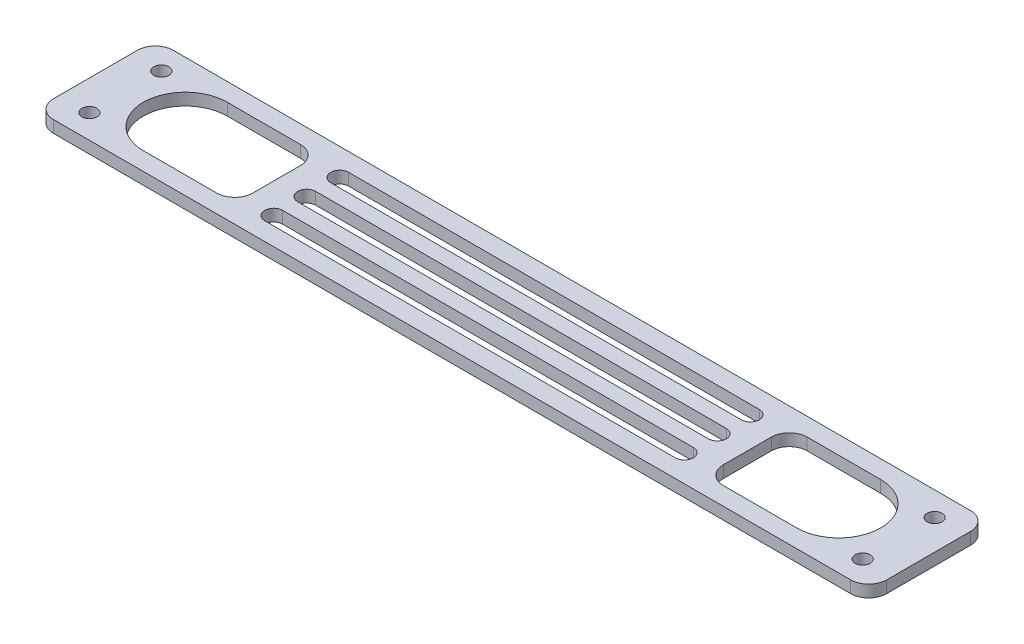
SolidWorks part; units mm, degrees
material "Thornel Mat VMA"
ref_plane "前视基准面" through (0, 0, 0) normal (0, 0, 1) x (1, 0, 0)
ref_plane "上视基准面" through (0, 0, 0) normal (0, 1, 0) x (1, 0, 0)
ref_plane "右视基准面" through (0, 0, 0) normal (1, 0, 0) x (0, 0, -1)
sketch "草图1" plane through (0, 0, 0) normal (0, 1, 0) x (1, 0, 0)
  line L1 (66.5, 10) -> (-66.5, 10)
  line L2 (69.5, 7) -> (69.5, -7)
  line L3 (66.5, -10) -> (-66.5, -10)
  line L4 (-69.5, 7) -> (-69.5, -7)
  line L5 (69.5, 10) -> (-69.5, -10) construction
  line L6 (69.5, -10) -> (-69.5, 10) construction
  arc A0 (69.5, 7) -> (66.5, 10) centre (66.5, 7) ccw
  arc A1 (69.5, -7) -> (66.5, -10) centre (66.5, -7) cw
  arc A2 (-66.5, -10) -> (-69.5, -7) centre (-66.5, -7) cw
  arc A3 (-66.5, 10) -> (-69.5, 7) centre (-66.5, 7) ccw
  point P0 (0, 0)
  dimension "D3" = 3
  dimension "D1" = 20
  dimension "D2" = 139
extrude "凸台-拉伸1" add sketch "草图1" along normal blind 2
sketch "草图2" plane through (0, 2, 0) normal (0, 1, 0) x (1, 0, 0)
  line L1 (64.5, 6) -> (-64.5, 6)
  line L2 (64.5, 6) -> (64.5, -6)
  line L3 (64.5, -6) -> (-64.5, -6)
  line L4 (-64.5, 6) -> (-64.5, -6)
  line L5 (64.5, 6) -> (-64.5, -6) construction
  line L6 (64.5, -6) -> (-64.5, 6) construction
  point P0 (0, 0)
  dimension "D1" = 12
  dimension "D2" = 129
hole_wizard "孔1" positions "草图3" profile "草图4" legacy end condition through all
sketch "草图3" plane through (0, 2, 0) normal (0, 1, 0) x (1, 0, 0)
  point P0 (-64.5, 6)
  point P3 (-64.5, -6)
  point P6 (64.5, -6)
  point P9 (64.5, 6)
sketch "草图4" plane through (-64.5, 2, -6) normal (1, 0, 0) x (0, 0, 1)
  line L0 (0, 0) -> (0, 2)
  line L1 (0, 2) -> (1.25, 2)
  line L2 (1.25, 2) -> (1.25, 0)
  line L3 (1.25, 0) -> (0, 0)
  line L4 (0, 110) -> (0, -10) construction
  dimension "直径" = 2.5
  dimension "深度" = 2
sketch "草图5" plane through (0, 2, 0) normal (0, 1, 0) x (1, 0, 0)
  line L0 (-54.5, 0) -> (54.5, 0) construction
  line L1 (-54.5, 7) -> (54.5, 7)
  line L2 (-54.5, -7) -> (54.5, -7)
  line L3 (66.5, 10) -> (-66.5, 10) construction
  line L4 (-69.5, 7) -> (-69.5, -7) construction
  arc A0 (-54.5, 7) -> (-54.5, -7) centre (-54.5, 0) ccw
  arc A1 (54.5, -7) -> (54.5, 7) centre (54.5, 0) ccw
  point P3 (0, 0)
  point P8 (0, 0)
  point P11 (-55.1605, 0)
  dimension "D1" = 3
  dimension "D2" = 15
extrude "切除-拉伸1" cut sketch "草图5" against normal through all
sketch "草图6" plane through (0, 0, 0) normal (0, -1, 0) x (1, 0, 0)
  line L0 (-66.5, 10) -> (66.5, 10) construction
  line L1 (-39.25, -10) -> (39.25, -10)
  line L2 (-39.25, -4) -> (-39.25, 4)
  line L3 (-39.25, 10) -> (39.25, 10)
  line L4 (39.25, -4) -> (39.25, 4)
  line L5 (-39.25, -10) -> (39.25, 10) construction
  line L6 (-39.25, 10) -> (39.25, -10) construction
  line L7 (39.25, -23.75) -> (39.25, 23.75) construction
  line L8 (39.25, 10) -> (46.786, 7)
  line L9 (-54.5, 7) -> (54.5, 7) construction
  line L10 (46.786, 7) -> (42.25, 7)
  line L11 (39.25, -10) -> (46.786, -7)
  line L12 (54.5, -7) -> (-54.5, -7) construction
  line L13 (46.786, -7) -> (42.25, -7)
  line L14 (-39.25, 10) -> (-46.786, 7)
  line L15 (-46.786, 7) -> (-42.25, 7)
  line L16 (-39.25, -10) -> (-46.4944, -7)
  line L17 (-46.4944, -7) -> (-42.25, -7)
  line L18 (-39.25, 23.75) -> (-39.25, -23.75) construction
  arc A0 (39.25, -4) -> (42.25, -7) centre (42.25, -4) ccw
  arc A1 (39.25, 4) -> (42.25, 7) centre (42.25, 4) cw
  arc A2 (-42.25, -7) -> (-39.25, -4) centre (-42.25, -4) ccw
  arc A3 (-39.25, 4) -> (-42.25, 7) centre (-42.25, 4) ccw
  point P0 (0, 0)
  point P26 (39.25, -7)
  point P29 (39.25, 7)
  point P32 (-39.25, -7)
  point P35 (-39.25, 7)
  dimension "D1" = 3
extrude "凸台-拉伸2" add sketch "草图6" against normal blind 2
sketch "草图7" plane through (0, 0, 0) normal (0, -1, 0) x (1, 0, 0)
  line L0 (34.25, 0) -> (-34.25, 0) construction
  line L1 (34.25, -1.5) -> (-34.25, -1.5)
  line L2 (34.25, 1.5) -> (-34.25, 1.5)
  line L3 (39.25, -4) -> (39.25, 4) construction
  line L4 (34.25, 5.5) -> (-34.25, 5.5) construction
  line L5 (34.25, 4) -> (-34.25, 4)
  line L6 (34.25, 7) -> (-34.25, 7)
  line L7 (34.25, -5.5) -> (-34.25, -5.5) construction
  line L8 (34.25, -7) -> (-34.25, -7)
  line L9 (34.25, -4) -> (-34.25, -4)
  arc A0 (34.25, -1.5) -> (34.25, 1.5) centre (34.25, 0) ccw
  arc A1 (-34.25, 1.5) -> (-34.25, -1.5) centre (-34.25, 0) ccw
  arc A2 (34.25, 4) -> (34.25, 7) centre (34.25, 5.5) ccw
  arc A3 (-34.25, 7) -> (-34.25, 4) centre (-34.25, 5.5) ccw
  arc A4 (34.25, -7) -> (34.25, -4) centre (34.25, -5.5) ccw
  arc A5 (-34.25, -4) -> (-34.25, -7) centre (-34.25, -5.5) ccw
  point P3 (0, 0)
  point P14 (0, 5.5)
  point P21 (0, -5.5)
  dimension "D1" = 1.5
  dimension "D2" = 5
  dimension "D4" = 5.5
  dimension "D3" = 2
  dimension "D5" = 2
extrude "切除-拉伸2" cut sketch "草图7" against normal through all both and the other way through all
